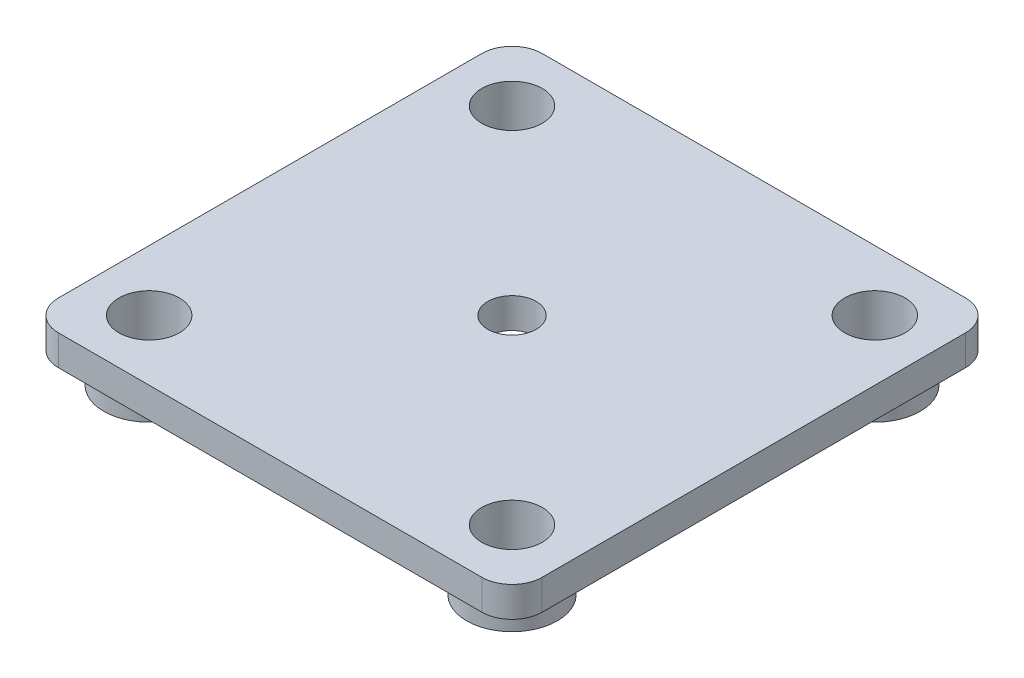
SolidWorks part; units mm, degrees
ref_plane "Front" through (0, 0, 0) normal (0, 0, 1) x (1, 0, 0)
ref_plane "Top" through (0, 0, 0) normal (0, 1, 0) x (1, 0, 0)
ref_plane "Right" through (0, 0, 0) normal (1, 0, 0) x (0, 0, -1)
sketch "Sketch1" plane through (0, 0, 0) normal (0, 1, 0) x (1, 0, 0)
  line L1 (-40, 40) -> (40, 40)
  line L2 (-40, 40) -> (-40, -40)
  line L3 (-40, -40) -> (40, -40)
  line L4 (40, 40) -> (40, -40)
  line L5 (-40, 40) -> (40, -40) construction
  line L6 (-40, -40) -> (40, 40) construction
  line L7 (-30, 30) -> (30, 30) construction
  line L8 (-30, 30) -> (-30, -30) construction
  line L9 (-30, -30) -> (30, -30) construction
  line L10 (30, 30) -> (30, -30) construction
  line L11 (-30, 30) -> (30, -30) construction
  line L12 (-30, -30) -> (30, 30) construction
  circle A0 centre (-30, 30) radius 5
  circle A1 centre (30, 30) radius 5
  circle A2 centre (30, -30) radius 5
  circle A3 centre (-30, -30) radius 5
  point P0 (0, 0)
  point P6 (0, 0)
  dimension "D3" = 10
  dimension "D1" = 60
  dimension "D2" = 10
extrude "Boss-Extrude1" add sketch "Sketch1" along normal blind 5
sketch "Sketch2" plane through (0, 0, 0) normal (0, -1, 0) x (1, 0, 0)
  circle A0 centre (-30, -30) radius 5 construction
  circle A1 centre (30, -30) radius 5 construction
  circle A2 centre (30, 30) radius 5 construction
  circle A3 centre (-30, 30) radius 5 construction
  circle A4 centre (-30, -30) radius 5
  circle A5 centre (30, -30) radius 5
  circle A6 centre (30, 30) radius 5
  circle A7 centre (-30, 30) radius 5
extrude "Extrude-Thin1" add sketch "Sketch2" along normal blind 5 thin thin type one direction wall 2.5
sketch "Sketch3" plane through (0, 5, 0) normal (0, 1, 0) x (1, 0, 0)
  circle A0 centre (0, 0) radius 4
  dimension "D1" = 8
extrude "Cut-Extrude1" cut sketch "Sketch3" against normal through all
fillet "Fillet1" radius 5 4 edges at (-40, 2.5, 40) (-40, 2.5, -40) (40, 2.5, 40) (40, 2.5, -40)
